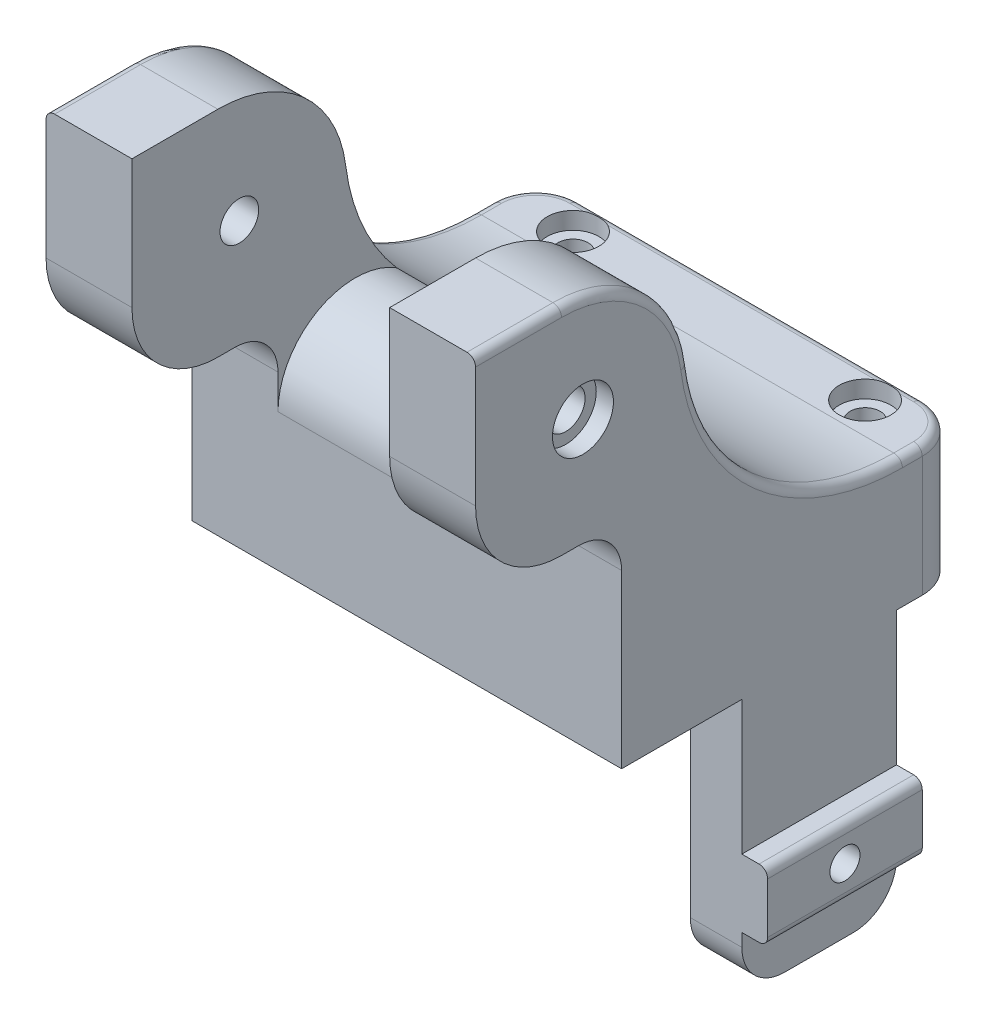
SolidWorks part; units mm, degrees
ref_plane "Alzado" through (0, 0, 0) normal (0, 0, 1) x (1, 0, 0)
ref_plane "Planta" through (0, 0, 0) normal (0, 1, 0) x (1, 0, 0)
ref_plane "Vista lateral" through (0, 0, 0) normal (1, 0, 0) x (0, 0, -1)
sketch "Croquis1" plane through (0, 0, 0) normal (0, 1, 0) x (1, 0, 0)
  line L1 (0, 0) -> (50, 0)
  line L2 (0, 0) -> (0, 40)
  line L3 (0, 40) -> (50, 40)
  line L4 (50, 0) -> (50, 40)
  dimension "D1" = 50
  dimension "D2" = 40
extrude "Saliente-Extruir1" add sketch "Croquis1" along normal blind 25
sketch "Croquis4" plane through (0, 25, 0) normal (0, 1, 0) x (1, 0, 0)
  line L0 (0, 40) -> (0, 0) construction
  line L1 (0, 8) -> (10, 8)
  line L2 (0, 8) -> (0, -17)
  line L3 (0, -17) -> (10, -17)
  line L4 (10, 8) -> (10, -17)
  line L5 (50, 0) -> (50, 40) construction
  line L6 (50, 8) -> (40, 8)
  line L7 (50, 8) -> (50, -17)
  line L8 (50, -17) -> (40, -17)
  line L9 (40, 8) -> (40, -17)
  line L10 (50, 40) -> (0, 40) construction
  dimension "D1" = 10
  dimension "D2" = 10
  dimension "D3" = 25
  dimension "D4" = 25
  dimension "D5" = 32
  dimension "D6" = 32
extrude "Saliente-Extruir3" add sketch "Croquis4" along normal blind 25
sketch "Croquis5" plane through (50, 0, 0) normal (1, 0, 0) x (0, 0, -1)
  line L0 (8, 50) -> (-17, 25) construction
  circle A0 centre (-4.5, 37.5) radius 2.25
  dimension "D1" = 4.5
extrude "Cortar-Extruir2" cut sketch "Croquis5" against normal up to surface (50 mm away) up to face at (0, 25, -7.75)
fillet "Redondeo4" radius 15 2 edges at (5, 50, -8) (45, 50, -8)
fillet "Redondeo5" radius 10 2 edges at (5, 25, 17) (45, 25, 17)
fillet "Redondeo6" radius 9 1 edges at (25, 25, 0)
sketch "Croquis6" plane through (0, 25, 0) normal (0, 1, 0) x (1, 0, 0)
  line L4 (0, 40) -> (0, 9)
  line L5 (0, 9) -> (50, 9)
  line L6 (50, 9) -> (50, 40)
  line L7 (50, 40) -> (0, 40)
  line L8 (0, 40) -> (0, 9)
  line L9 (0, 9) -> (50, 9)
  line L10 (50, 9) -> (50, 40)
  line L11 (50, 40) -> (0, 40)
  dimension "D1" = 0
extrude "Cortar-Extruir3" cut sketch "Croquis6" against normal blind 10
sketch "Croquis7" plane through (0, 0, -9) normal (0, 0, -1) x (-1, 0, 0)
  line L4 (0, 25) -> (-50, 25)
  line L5 (-50, 25) -> (-50, 15)
  line L6 (-50, 15) -> (0, 15)
  line L7 (0, 15) -> (0, 25)
  line L8 (0, 25) -> (-50, 25)
  line L9 (-50, 25) -> (-50, 15)
  line L10 (-50, 15) -> (0, 15)
  line L11 (0, 15) -> (0, 25)
  dimension "D1" = 0
extrude "Cortar-Extruir4" cut sketch "Croquis7" against normal up to surface (1 mm away) up to face at (5, 29.9721, -8)
fillet "Redondeo7" radius 25 1 edges at (25, 15, -8)
fillet "Redondeo8" radius 5 2 edges at (45, 25, 0) (5, 25, 0)
sketch "Croquis8" plane through (0, 15, 0) normal (0, 1, 0) x (1, 0, 0)
  line L0 (0, 36.3431) -> (50, 36.3431) construction
  line L1 (0, 40) -> (0, 32.6863) construction
  line L2 (50, 32.6863) -> (50, 40) construction
  circle A0 centre (8, 36.3431) radius 1.75
  circle A1 centre (42, 36.3431) radius 1.75
  dimension "D1" = 3.5
  dimension "D2" = 3.5
  dimension "D3" = 8
  dimension "D4" = 8
extrude "Cortar-Extruir5" cut sketch "Croquis8" against normal up to surface (15 mm away) up to face at (25, 0, -20)
sketch "Croquis9" plane through (0, 15, 0) normal (0, 1, 0) x (1, 0, 0)
  circle A0 centre (8, 36.3431) radius 3
  circle A1 centre (42, 36.3431) radius 3
  dimension "D1" = 6
  dimension "D2" = 6
extrude "Cortar-Extruir6" cut sketch "Croquis9" against normal blind 2
fillet "Redondeo9" radius 5 2 edges at (0, 7.5, -40) (50, 7.5, -40)
sketch "Croquis10" plane through (0, 0, 0) normal (0, -1, 0) x (1, 0, 0)
  line L0 (0, -35) -> (0, 0) construction
  line L1 (0, -32) -> (6, -32)
  line L2 (0, -32) -> (0, -14)
  line L3 (0, -14) -> (6, -14)
  line L4 (6, -32) -> (6, -14)
  line L5 (45, -40) -> (5, -40) construction
  dimension "D1" = 18
  dimension "D2" = 8
  dimension "D3" = 6
extrude "Saliente-Extruir4" add sketch "Croquis10" along normal blind 30
sketch "Croquis11" plane through (0, 0, 0) normal (-1, 0, 0) x (0, 0, 1)
  line L0 (-32, -30) -> (-32, 0) construction
  line L1 (-32, -23.5) -> (-14, -23.5)
  line L2 (-32, -23.5) -> (-32, -15.6)
  line L3 (-32, -15.6) -> (-14, -15.6)
  line L4 (-14, -23.5) -> (-14, -15.6)
  line L5 (-14, -30) -> (-14, 0) construction
  line L6 (-14, -30) -> (-32, -30) construction
  dimension "D1" = 6.5
  dimension "D2" = 7.9
extrude "Saliente-Extruir5" add sketch "Croquis11" along normal blind 3
fillet "Redondeo10" radius 1 2 edges at (-3, -23.5, -23) (-3, -15.6, -23)
sketch "Croquis12" plane through (-3, 0, 0) normal (-1, 0, 0) x (0, 0, 1)
  line L0 (-32, -19.55) -> (-14, -19.55) construction
  line L1 (-32, -16.6) -> (-32, -22.5) construction
  line L2 (-14, -22.5) -> (-14, -16.6) construction
  circle A0 centre (-28, -19.55) radius 1.75
  circle A1 centre (-18, -19.55) radius 1.75
  dimension "D1" = 3.5
  dimension "D2" = 3.5
  dimension "D3" = 4
  dimension "D4" = 4
extrude "Cortar-Extruir7" cut sketch "Croquis12" against normal up to surface (9 mm away) up to face at (6, -15, -23)
sketch "Croquis13" plane through (6, 0, 0) normal (1, 0, 0) x (0, 0, -1)
  circle A0 centre (28, -19.55) radius 3
  circle A1 centre (18, -19.55) radius 3
  dimension "D1" = 6
  dimension "D2" = 6
extrude "Cortar-Extruir8" cut sketch "Croquis13" against normal blind 1.5
sketch "Croquis16" plane through (0, 0, 0) normal (0, -1, 0) x (1, 0, 0)
  line L0 (25, -40) -> (25, 0) construction
  line L1 (45, -40) -> (5, -40) construction
  line L2 (0, 0) -> (50, 0) construction
  circle A0 centre (25, -25.3431) radius 1.75
  circle A1 centre (8, -36.3431) radius 1.75 construction
  dimension "D1" = 3.5
  dimension "D2" = 11
extrude "Cortar-Extruir9" cut sketch "Croquis16" against normal through all
ref_plane "Plano1" through (0, 20, 0) normal (0, 1, 0) x (1, 0, 0)
sketch "Croquis17" plane through (0, 20, 0) normal (0, 1, 0) x (1, 0, 0)
  circle A0 centre (25, 25.3431) radius 3
  dimension "D1" = 6
extrude "Cortar-Extruir10" cut sketch "Croquis17" against normal blind 5.5
fillet "Redondeo11" radius 5 2 edges at (3, -30, -14) (3, -30, -32)
fillet "Redondeo12" radius 1 11 edges at (50, 50, 12) (50, 46.25, -2.9216) (50, 21.25, -16.1503) (50, 15, -33.8431) (48.5355, 15, -38.5355) (0, 50, 12) (0, 46.25, -2.9216) (0, 21.25, -16.1503) (0, 15, -33.8431) (1.4645, 15, -38.5355) (25, 15, -40)
sketch "Croquis18" plane through (0, 0, 0) normal (0, -1, 0) x (1, 0, 0)
  line L0 (50, 0) -> (50, -35) construction
  line L1 (50, -32) -> (44, -32)
  line L2 (50, -32) -> (50, -14)
  line L3 (50, -14) -> (44, -14)
  line L4 (44, -32) -> (44, -14)
  line L5 (45, -40) -> (5, -40) construction
  dimension "D1" = 18
  dimension "D2" = 6
  dimension "D3" = 8
extrude "Saliente-Extruir6" add sketch "Croquis18" along normal blind 30
sketch "Croquis19" plane through (50, 0, 0) normal (1, 0, 0) x (0, 0, -1)
  line L0 (32, -30) -> (32, 0) construction
  line L1 (32, -15.6) -> (14, -15.6)
  line L2 (32, -15.6) -> (32, -23.5)
  line L3 (32, -23.5) -> (14, -23.5)
  line L4 (14, -15.6) -> (14, -23.5)
  line L5 (14, -30) -> (14, 0) construction
  line L6 (32, -30) -> (14, -30) construction
  point P8 (23, -23.5)
  dimension "D1" = 7.9
  dimension "D2" = 6.5
extrude "Saliente-Extruir7" add sketch "Croquis19" along normal blind 3
sketch "Croquis20" plane through (53, 0, 0) normal (1, 0, 0) x (0, 0, -1)
  line L0 (32, -19.55) -> (14, -19.55) construction
  line L1 (32, -23.5) -> (32, -15.6) construction
  line L2 (14, -15.6) -> (14, -23.5) construction
  line L3 (23, -23.5) -> (23, -15.6) construction
  line L4 (14, -23.5) -> (32, -23.5) construction
  line L5 (32, -15.6) -> (14, -15.6) construction
  circle A0 centre (23, -19.55) radius 1.75
  point P8 (23, -19.55)
  point P9 (23, -19.55)
  dimension "D1" = 3.5
extrude "Cortar-Extruir11" cut sketch "Croquis20" against normal up to surface (9 mm away) up to face at (44, -15, -23)
sketch "Croquis21" plane through (44, 0, 0) normal (-1, 0, 0) x (0, 0, 1)
  circle A0 centre (-23, -19.55) radius 3
  dimension "D1" = 6
extrude "Cortar-Extruir12" cut sketch "Croquis21" against normal blind 1.5
fillet "Redondeo13" radius 1 2 edges at (53, -15.6, -23) (53, -23.5, -23)
fillet "Redondeo14" radius 5 2 edges at (47, -30, -14) (47, -30, -32)
sketch "Croquis22" plane through (0, 0, -32) normal (0, 0, -1) x (-1, 0, 0)
  line L1 (-6, 0) -> (3.2219, 0)
  line L2 (-6, 0) -> (-6, -30.8775)
  line L3 (-6, -30.8775) -> (3.2219, -30.8775)
  line L4 (3.2219, 0) -> (3.2219, -30.8775)
extrude "Cortar-Extruir13" cut sketch "Croquis22" against normal through all
sketch "Croquis23" plane through (50, 0, 0) normal (1, 0, 0) x (0, 0, -1)
  circle A0 centre (-4.5, 37.5) radius 3.55
  dimension "D1" = 7.1
extrude "Cortar-Extruir14" cut sketch "Croquis23" against normal blind 2
sketch "Croquis24" plane through (0, 0, 0) normal (-1, 0, 0) x (0, 0, 1)
  line L0 (17, 49) -> (7, 49) construction
  line L1 (0.2853, 37.5) -> (2.3927, 33.85)
  line L2 (2.3927, 33.85) -> (6.6073, 33.85)
  line L3 (6.6073, 33.85) -> (8.7147, 37.5)
  line L4 (8.7147, 37.5) -> (6.6073, 41.15)
  line L5 (6.6073, 41.15) -> (2.3927, 41.15)
  line L6 (2.3927, 41.15) -> (0.2853, 37.5)
  circle A0 centre (4.5, 37.5) radius 3.65 construction
  dimension "D1" = 7.3
extrude "Cortar-Extruir15" cut sketch "Croquis24" against normal blind 2
